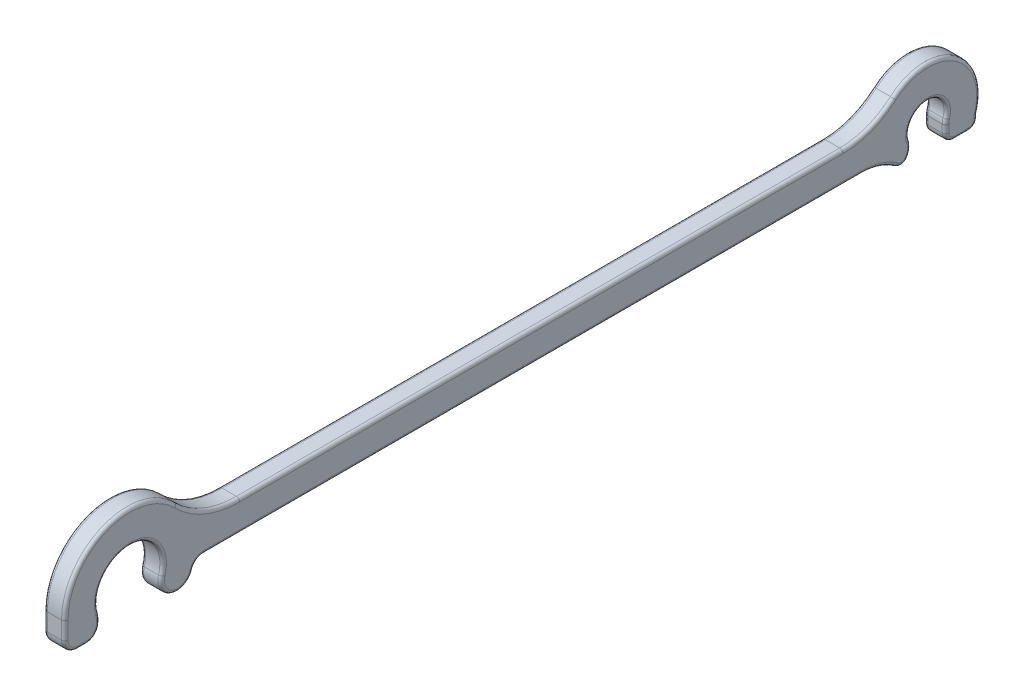
SolidWorks part; units mm, degrees
ref_plane "Front Plane" through (0, 0, 0) normal (0, 0, 1) x (1, 0, 0)
ref_plane "Top Plane" through (0, 0, 0) normal (0, 1, 0) x (1, 0, 0)
ref_plane "Right Plane" through (0, 0, 0) normal (1, 0, 0) x (0, 0, -1)
sketch "Sketch1" plane through (0, 0, 0) normal (1, 0, 0) x (0, 0, -1)
  line L0 (0, 0) -> (36.5, 0) construction
  line L1 (4.999, 0.9) -> (32.607, 0.9)
  line L2 (3.3657, -0.5) -> (33.4646, -0.5)
  line L3 (38.7598, -0.7308) -> (38.7598, -0.85)
  line L4 (38.3598, -1.25) -> (37.6962, -1.25)
  line L5 (37.2962, -0.85) -> (37.2962, -0.5)
  line L6 (-2.1541, -0.65) -> (2.1541, -0.65) construction
  line L7 (-3, 0) -> (-3, -0.8)
  line L8 (-2.4, -1.4) -> (-2.0041, -1.4)
  line L9 (-1.4041, -0.8) -> (-1.4041, -0.65)
  circle A0 centre (0, 0) radius 1.5 construction
  circle A1 centre (36.5, 0) radius 0.875 construction
  arc A2 (34.9538, -0.5) -> (38.0462, -0.5) centre (36.5, 0) cw construction
  arc A3 (38.7598, -0.7308) -> (34.2402, -0.7308) centre (36.5, 0) ccw construction
  arc A4 (37.3326, -0.2692) -> (35.6674, -0.2692) centre (36.5, 0) ccw construction
  arc A5 (37.3326, -0.2692) -> (38.7598, -0.7308) centre (38.0462, -0.5) ccw construction
  arc A6 (34.2402, -0.7308) -> (35.6674, -0.2692) centre (34.9538, -0.5) ccw construction
  arc A7 (38.7598, -0.85) -> (38.3598, -1.25) centre (38.3598, -0.85) cw
  arc A8 (37.6962, -1.25) -> (37.2962, -0.85) centre (37.6962, -0.85) cw
  circle A11 centre (35.271, -0.7) radius 0.375 construction
  arc A12 (33.4646, -0.5) -> (35.0543, -1.006) centre (33.4646, -3.25) cw
  arc A13 (32.607, 0.9) -> (34.9262, 1.7787) centre (32.607, 4.4) ccw
  arc A14 (35.0543, -1.006) -> (35.5883, -0.9) centre (35.271, -0.7) ccw
  arc A15 (35.5883, -0.9) -> (35.6674, -0.2692) centre (34.9538, -0.5) ccw
  arc A16 (35.6674, -0.2692) -> (37.3326, -0.2692) centre (36.5, 0) cw
  arc A17 (37.3326, -0.2692) -> (37.2962, -0.5) centre (38.0462, -0.5) ccw
  arc A18 (34.9262, 1.7787) -> (38.7598, -0.7308) centre (36.5, 0) cw
  arc A19 (2.1541, -0.65) -> (-2.1541, -0.65) centre (0, 0) ccw construction
  arc A20 (2.8721, -0.8667) -> (-2.8721, -0.8667) centre (0, 0) ccw construction
  arc A21 (1.436, -0.4333) -> (-1.436, -0.4333) centre (0, 0) ccw construction
  arc A22 (1.436, -0.4333) -> (2.8721, -0.8667) centre (2.1541, -0.65) ccw construction
  arc A23 (-2.8721, -0.8667) -> (-1.436, -0.4333) centre (-2.1541, -0.65) ccw construction
  arc A24 (-3, -0.8) -> (-2.4, -1.4) centre (-2.4, -0.8) ccw
  arc A25 (-2.0041, -1.4) -> (-1.4041, -0.8) centre (-2.0041, -0.8) ccw
  arc A26 (3.3657, -0.5) -> (2.8721, -0.8667) centre (3.3657, -1.0156) ccw
  arc A27 (2.1424, 2.1) -> (4.999, 0.9) centre (4.999, 4.9) ccw
  arc A28 (-3, 0) -> (2.1424, 2.1) centre (0, 0) cw
  arc A29 (-1.436, -0.4333) -> (-1.4041, -0.65) centre (-2.1541, -0.65) cw
  arc A30 (2.8721, -0.8667) -> (1.436, -0.4333) centre (2.1541, -0.65) cw
  arc A31 (-1.436, -0.4333) -> (1.436, -0.4333) centre (0, 0) cw
  point P11 (36.5, 1.625)
  point P40 (0, 2.25)
  dimension "D2" = 3
  dimension "D3" = 1.75
  dimension "D6" = 0.75
  dimension "D7" = 0.4
  dimension "D8" = 0.2
  dimension "D10" = 2.75
  dimension "D9" = 0.75
  dimension "D11" = 3.5
  dimension "D12" = 0.75
  dimension "D14" = 0.6
  dimension "D15" = 4
  dimension "D1" = 36.5
  dimension "D4" = 0.9
  dimension "D5" = 0.5
  dimension "D13" = 0.15
base flange "Base-Flange1" sketch "Sketch1" thickness 0.95 reverse thickness direction no parameters "D1"=0.7366
fillet "Fillet1" radius 0.15 50 edges at (-0.95, 1.9871, -37.8008) (-0.95, 1.127, -33.847) (-0.95, -0.7904, -38.7598) (-0.95, -1.1328, -38.6426) (-0.95, -1.25, -38.028) (-0.95, -1.1328, -37.4133) (-0.95, -0.675, -37.2962) (-0.95, -0.3832, -37.3053) (-0.95, 0.875, -36.5) (-0.95, -0.5934, -35.698) (-0.95, -1.0678, -35.3441) (-0.95, -0.6296, -34.2988) (-0.95, -0.5, -18.4152) (-0.95, -0.6017, -3.0583) (-0.95, -1.368, -1.9374) (-0.95, 1.5, 0) (-0.95, -0.5405, 1.4121) (-0.95, -0.725, 1.4041) (-0.95, -1.2243, 1.5798) (-0.95, -1.4, 2.202) (-0.95, -1.2243, 2.8243) (-0.95, -0.4, 3) (-0.95, 2.7773, 1.1342) (-0.95, 1.2122, -3.4498) (0, 1.9871, -37.8008) (0, 1.127, -33.847) (0, -0.7904, -38.7598) (0, -1.1328, -38.6426) (0, -1.25, -38.028) (0, -1.1328, -37.4133) (0, -0.675, -37.2962) (0, -0.3832, -37.3053) (0, 0.875, -36.5) (0, -0.5934, -35.698) (0, -1.0678, -35.3441) (0, -0.6296, -34.2988) (0, -0.5, -18.4152) (0, -0.6017, -3.0583) (0, -1.368, -1.9374) (0, 1.5, 0) (0, -0.5405, 1.4121) (0, -0.725, 1.4041) (0, -1.2243, 1.5798) (0, -1.4, 2.202) (0, -1.2243, 2.8243) (0, -0.4, 3) (0, 2.7773, 1.1342) (0, 1.2122, -3.4498) (-0.95, 0.9, -18.803) (0, 0.9, -18.803)
sketch "Bend-Lines1" [suppressed] plane through (0, 0, 0) normal (0, 1, 0) x (1, 0, 0)
sketch "Bounding-Box1" [suppressed] plane through (0, 0, 0) normal (0, 1, 0) x (1, 0, 0)
sheet metal parameters "Sheet-Metal1" thickness 0.95 parameters "D1"=0.7366
flat pattern "Flat-Pattern1" [suppressed]
sketch "Bend-Lines2" plane through (0, 0, 0) normal (0, 1, 0) x (1, 0, 0)
sketch3d "Bounding-Box2" [suppressed]
  line L0 (-7.999, -6.3, 0) -> (33.876, -6.3, 0) construction
  line L1 (-7.999, -1.9, 0) -> (33.876, -1.9, 0) construction
  line L2 (-7.999, -6.3, 0) -> (-7.999, -1.9, 0) construction
  line L3 (33.876, -6.3, 0) -> (33.876, -1.9, 0) construction
